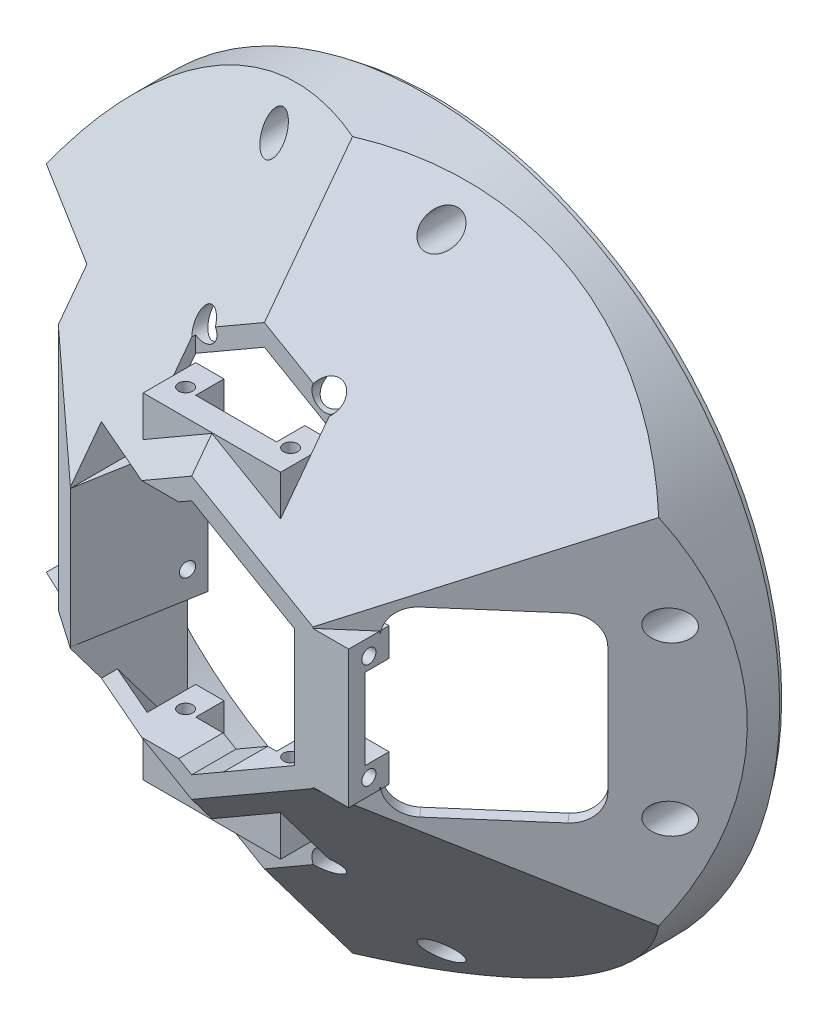
SolidWorks part; units mm, degrees
ref_plane "Front Plane" through (0, 0, 0) normal (0, 0, 1) x (1, 0, 0)
ref_plane "Top Plane" through (0, 0, 0) normal (0, 1, 0) x (1, 0, 0)
ref_plane "Right Plane" through (0, 0, 0) normal (1, 0, 0) x (0, 0, -1)
sketch "Sketch1" plane through (0, 0, 0) normal (0, 0, 1) x (1, 0, 0)
  circle A0 centre (0, 0) radius 87.5
  dimension "D1" = 175
extrude "Boss-Extrude1" add sketch "Sketch1" along normal blind 60
sketch "Sketch2" plane through (0, 0, 0) normal (0, 1, 0) x (1, 0, 0)
  line L0 (-73.4655, -109.9854) -> (-130.9655, -59.9854)
  line L1 (-73.4655, -109.9854) -> (-30, -60)
  line L2 (-130.9655, -59.9854) -> (-87.5, -10)
  line L3 (-30, -60) -> (-87.5, -10)
  line L4 (-73.4655, -109.9854) -> (-87.5, -10) construction
  line L5 (-130.9655, -59.9854) -> (-30, -60) construction
  line L7 (-87.5, 0) -> (-87.5, -60) construction
  line L8 (-87.5, -60) -> (87.5, -60) construction
  point P1 (-80.4828, -59.9927)
  dimension "D1" = 30
  dimension "D2" = 10
extrude "Cut-Extrude1" cut sketch "Sketch2" against normal through all and the other way through all
pattern_circular "CirPattern1" count 6 over 360 about axis through (0, 0, 0) along (0, 0, 1) of "Cut-Extrude1"
shell "Shell1" thickness 3 removed face at (87.5, 0, 0) removed face at (0, 0, 60)
sketch "Sketch3" plane through (0, 0, 0) normal (0, 0, -1) x (-1, 0, 0)
  circle A0 centre (0, 0) radius 87.5 construction
  circle A1 centre (0, 0) radius 87.5
  circle A2 centre (0, 0) radius 86
  dimension "D1" = 1.5
extrude "Cut-Extrude2" cut sketch "Sketch3" against normal blind 2
sketch "Sketch4" plane through (0, 0, 0) normal (0, 0, 1) x (1, 0, 0)
  line L8 (-53, 40) -> (-53, -40)
  line L9 (-30, -17.3205) -> (-30, 17.3205) construction
  line L10 (-75.7772, 43.75) -> (-53, 40)
  line L11 (-53, -40) -> (-75.7772, -43.75)
  line L12 (-53, 0) -> (0, 0) construction
  arc A1 (-75.7772, 43.75) -> (-75.7772, -43.75) centre (0, 0) ccw construction
  arc A2 (-75.7772, 43.75) -> (-75.7772, -43.75) centre (0, 0) ccw
  dimension "D1" = 23
  dimension "D2" = 80
extrude "Cut-Extrude3" cut sketch "Sketch4" along normal through all
sketch "Sketch5" plane through (0, 0, 0) normal (0, 0, 1) x (1, 0, 0)
  line L0 (0, 0) -> (-20.7055, 77.2741) construction
  line L1 (0, 84.5) -> (0, 29.3618) construction
  line L2 (-23.5083, 73.1335) -> (-31.3758, 78.459)
  line L3 (-16.208, 75.0896) -> (-12.0573, 83.6354)
  line L4 (-31.3758, 78.459) -> (-12.0573, 83.6354) construction
  line L5 (-21.7165, 81.0472) -> (-20.7055, 77.2741) construction
  arc A0 (-23.5083, 73.1335) -> (-16.208, 75.0896) centre (-20.7055, 77.2741) ccw
  arc A1 (-72.6058, -43.2279) -> (-72.6058, 43.2279) centre (0, 0) ccw construction
  arc A2 (0, 84.5) -> (-72.6058, 43.2279) centre (0, 0) ccw construction
  arc A3 (-12.0573, 83.6354) -> (-31.3758, 78.459) centre (0, 0) ccw
  dimension "D2" = 10
  dimension "D1" = 15
  dimension "D3" = 80
  dimension "D4" = 20
extrude "Boss-Extrude2" add sketch "Sketch5" along normal up to next
sketch "Sketch6" plane through (0, 0, 0) normal (0, 0, -1) x (-1, 0, 0)
  circle A0 centre (20.7055, 77.2741) radius 1.75
  dimension "D1" = 3.5
extrude "Cut-Extrude4" cut sketch "Sketch6" against normal through all
sketch "Sketch7" plane through (0, 0, 60) normal (0, 0, 1) x (1, 0, 0)
  circle A2 centre (-20.7055, 77.2741) radius 3.75
  circle A3 centre (-20.7055, 77.2741) radius 3.75
  dimension "D1" = 2
extrude "Cut-Extrude5" cut sketch "Sketch7" against normal blind 55
mirror "Mirror1" about plane through (0, 0, 0) normal (1, 0, 0) of "Cut-Extrude5", "Cut-Extrude4", "Boss-Extrude2"
pattern_circular "CirPattern2" count 3 every 90 about axis through (0, 0, 2) along (0, 0, -1) of "Mirror1"
sketch "Sketch8" plane through (42.6265, 0, 49.0205) normal (0.6562, 0, 0.7546) x (0.7546, 0, -0.6562)
  line L0 (0, 0) -> (15, 0) construction
  line L1 (2, 22.5) -> (28, 22.5)
  line L2 (-5, 15.5) -> (-5, -15.5)
  line L3 (2, -22.5) -> (28, -22.5)
  line L4 (35, 15.5) -> (35, -15.5)
  line L5 (-5, 22.5) -> (35, -22.5) construction
  line L6 (-5, -22.5) -> (35, 22.5) construction
  arc A0 (-5, -15.5) -> (2, -22.5) centre (2, -15.5) ccw
  arc A1 (28, -22.5) -> (35, -15.5) centre (28, -15.5) ccw
  arc A2 (28, 22.5) -> (35, 15.5) centre (28, 15.5) cw
  arc A3 (2, 22.5) -> (-5, 15.5) centre (2, 15.5) ccw
  point P0 (15, 0)
  dimension "D4" = 7
  dimension "D1" = 45
  dimension "D2" = 40
  dimension "D3" = 15
extrude "Cut-Extrude6" cut sketch "Sketch8" against normal through all
sketch "Sketch10" plane through (0, 0, 0) normal (0, 1, 0) x (1, 0, 0)
  line L0 (0, -20.1937) -> (0, -60) construction
  line L1 (-17, -42) -> (17, -42)
  line L2 (-17, -42) -> (-17, -55)
  line L3 (-17, -55) -> (17, -55)
  line L4 (17, -42) -> (17, -55)
  line L5 (-17, -42) -> (17, -55) construction
  line L6 (-17, -55) -> (17, -42) construction
  line L7 (0, -48.5) -> (0, 0) construction
  line L8 (0, -60) -> (30, -60) construction
  point P0 (0, -48.5)
  dimension "D1" = 13
  dimension "D2" = 34
  dimension "D3" = 5
extrude "Cut-Extrude8" cut sketch "Sketch10" against normal through all
sketch "Sketch12" plane through (0, 0, 42) normal (0, 0, 1) x (1, 0, 0)
  line L0 (17, -31.4656) -> (17, -48.7284) construction
  line L1 (-17, -31.4656) -> (17, -31.4656)
  line L2 (-17, -31.4656) -> (-17, -24.8261)
  line L4 (17, -31.4656) -> (17, -24.8261)
  line L5 (0, -41.2805) -> (17, -31.4656) construction
  line L6 (30, -17.3205) -> (0, -34.641) construction
  line L7 (0, -34.641) -> (-30, -17.3205) construction
  line L8 (-17, -24.8261) -> (-7.8561, -24.8261)
  line L9 (0, -29.3618) -> (-25.4281, -14.6809) construction
  line L10 (-7.8561, -24.8261) -> (0, -29.3618)
  line L11 (0, -29.3618) -> (7.8561, -24.8261)
  line L12 (25.4281, -14.6809) -> (0, -29.3618) construction
  line L13 (7.8561, -24.8261) -> (17, -24.8261)
extrude "Boss-Extrude4" add sketch "Sketch12" along normal up to next
sketch "Sketch13" plane through (0, -31.4656, 0) normal (0, -1, 0) x (1, 0, 0)
  line L0 (0, 42) -> (-17, 42) construction
  line L1 (-10, 42) -> (10, 42)
  line L2 (-10, 42) -> (-10, 49)
  line L3 (-10, 49) -> (10, 49)
  line L4 (10, 42) -> (10, 49)
  line L5 (0, 49) -> (0, 60) construction
  line L6 (-13, 48.5) -> (-17, 48.5) construction
  line L9 (-13, 48.5) -> (13, 48.5) construction
  line L10 (-17, 42) -> (-17, 55) construction
  line L11 (13, 48.5) -> (17, 48.5) construction
  line L12 (17, 55) -> (17, 42) construction
  circle A0 centre (-13, 48.5) radius 1.75
  circle A1 centre (13, 48.5) radius 1.75
  point P9 (0, 48.5)
  dimension "D4" = 3.5
  dimension "D1" = 7
  dimension "D2" = 20
  dimension "D3" = 26
extrude "Cut-Extrude9" cut sketch "Sketch13" against normal blind 8
sketch "Sketch14" plane through (0, -31.4656, 0) normal (0, -1, 0) x (1, 0, 0)
  line L13 (-17, 42) -> (-10, 42)
  line L14 (-10, 42) -> (-10, 49)
  line L15 (-10, 49) -> (10, 49)
  line L16 (10, 49) -> (10, 42)
  line L17 (10, 42) -> (17, 42)
  line L18 (17, 42) -> (17, 51.0244)
  line L19 (17, 51.0244) -> (17, 55)
  line L20 (17, 55) -> (7.8561, 55)
  line L21 (7.8561, 55) -> (0, 58.4157)
  line L22 (0, 58.4157) -> (-7.8561, 55)
  line L23 (-7.8561, 55) -> (-17, 55)
  line L24 (-17, 55) -> (-17, 51.0244)
  line L25 (-17, 51.0244) -> (-17, 42)
  line L26 (-17, 42) -> (-10, 42)
  line L27 (-10, 42) -> (-10, 49)
  line L28 (-10, 49) -> (10, 49)
  line L29 (10, 49) -> (10, 42)
  line L30 (10, 42) -> (17, 42)
  line L31 (17, 42) -> (17, 51.0244)
  line L32 (17, 51.0244) -> (17, 55)
  line L33 (17, 55) -> (-7.8561, 55)
  line L36 (-7.8561, 55) -> (-17, 55)
  line L37 (-17, 55) -> (-17, 51.0244)
  line L38 (-17, 51.0244) -> (-17, 42)
  circle A0 centre (13, 48.5) radius 1.75 construction
  circle A1 centre (-13, 48.5) radius 1.75 construction
  circle A2 centre (13, 48.5) radius 1.75
  circle A3 centre (-13, 48.5) radius 1.75
  dimension "D1" = 0
extrude "Boss-Extrude5" add sketch "Sketch14" along normal blind 10
mirror "Mirror2" about plane through (0, 0, 0) normal (0, 1, 0) of "Boss-Extrude5", "Cut-Extrude8", "Boss-Extrude4", "Cut-Extrude9"
sketch "Sketch15" plane through (0, 0, 0) normal (0, 0, 1) x (1, 0, 0)
  line L1 (-15, 50) -> (15, 50) construction
  line L2 (-15, 50) -> (-15, -50) construction
  line L3 (-15, -50) -> (15, -50) construction
  line L4 (15, 50) -> (15, -50) construction
  line L5 (-15, 50) -> (15, -50) construction
  line L6 (-15, -50) -> (15, 50) construction
  circle A0 centre (-15, 50) radius 3.25
  circle A1 centre (15, 50) radius 3.25
  circle A2 centre (15, -50) radius 3.25
  circle A3 centre (-15, -50) radius 3.25
  point P0 (0, 0)
  dimension "D1" = 6.5
  dimension "D2" = 100
  dimension "D3" = 30
extrude "Cut-Extrude10" cut sketch "Sketch15" along normal through all
sketch "Sketch16" plane through (0, 0, 60) normal (0, 0, 1) x (1, 0, 0)
  line L0 (25.4281, 14.6809) -> (25.4281, -14.6809) construction
  line L1 (25.4281, -17) -> (38.8535, -17)
  line L2 (25.4281, -17) -> (25.4281, 17)
  line L3 (25.4281, 17) -> (38.8535, 17)
  line L4 (38.8535, -17) -> (38.8535, 17)
  line L5 (38.8535, 15.5) -> (38.8535, -15.5) construction
  line L6 (25.4281, 0) -> (0, 0) construction
  dimension "D1" = 34
extrude "Boss-Extrude6" add sketch "Sketch16" against normal blind 10
sketch "Sketch17" plane through (38.8535, 0, 0) normal (1, 0, 0) x (0, 0, -1)
  line L0 (-55, 13) -> (-55, -13) construction
  line L1 (-55, 0) -> (0, 0) construction
  line L2 (-60, -17) -> (-60, 17) construction
  line L3 (-56, 10) -> (-46.4829, 10)
  line L4 (-56, 10) -> (-56, -10)
  line L5 (-56, -10) -> (-46.4829, -10)
  line L6 (-46.4829, 10) -> (-46.4829, -10)
  circle A0 centre (-55, 13) radius 1.75
  circle A1 centre (-55, -13) radius 1.75
  point P11 (-46.4829, 0)
  dimension "D5" = 3.5
  dimension "D1" = 26
  dimension "D2" = 20
  dimension "D3" = 1
  dimension "D4" = 5
extrude "Cut-Extrude11" cut sketch "Sketch17" against normal blind 37
sketch "Sketch18" plane through (0, 0, 60) normal (0, 0, 1) x (1, 0, 0)
  line L0 (-3.2248, 0) -> (0, 0) construction
  line L1 (-30, 27.5) -> (-3.2248, 27.5)
  line L2 (-30, 27.5) -> (-30, -27.5)
  line L3 (-30, -27.5) -> (-3.2248, -27.5)
  line L4 (-3.2248, 27.5) -> (-3.2248, -27.5)
  line L5 (0, -29.3618) -> (-7.8561, -24.8261) construction
  dimension "D1" = 55
extrude "Cut-Extrude12" cut sketch "Sketch18" against normal blind 37
sketch "Sketch19" plane through (0, 0, 0) normal (0, 1, 0) x (1, 0, 0)
  line L0 (-30, -56.0244) -> (-30, -31.0244)
  line L1 (-30, -31.0244) -> (-35, -31.0244)
  line L2 (-35, -31.0244) -> (-35, -51.6766)
  line L3 (-53, -36.0244) -> (-30, -56.0244) construction
  line L4 (-35, -51.6766) -> (-30, -56.0244)
  dimension "D1" = 25
  dimension "D2" = 5
extrude "Boss-Extrude7" add sketch "Sketch19" along normal up to next and the other way up to next
sketch "Sketch20" plane through (0, 0, 0) normal (0, 1, 0) x (1, 0, 0)
  line L0 (-30, -31.0244) -> (-24.8908, -31.0244)
  line L1 (-24.8908, -31.0244) -> (-30, -60)
  line L2 (-30, -60) -> (-30, -31.0244)
  dimension "D1" = 10
extrude "Boss-Extrude8" add sketch "Sketch20" along normal blind 17 and the other way blind 17
sketch "Sketch21" plane through (-18.8348, 0, -3.3211) normal (0.9848, 0, 0.1736) x (0.1736, 0, -0.9848)
  line L0 (-39.2979, 10.5) -> (-39.2979, -10.5) construction
  line L1 (-64.2979, -17) -> (-64.2979, 17) construction
  line L3 (-39.2979, 0) -> (0, 0) construction
  circle A0 centre (-39.2979, 10.5) radius 1.75
  circle A1 centre (-39.2979, -10.5) radius 1.75
  dimension "D1" = 3.5
  dimension "D2" = 21
  dimension "D3" = 25
extrude "Cut-Extrude13" cut sketch "Sketch21" against normal blind 25
